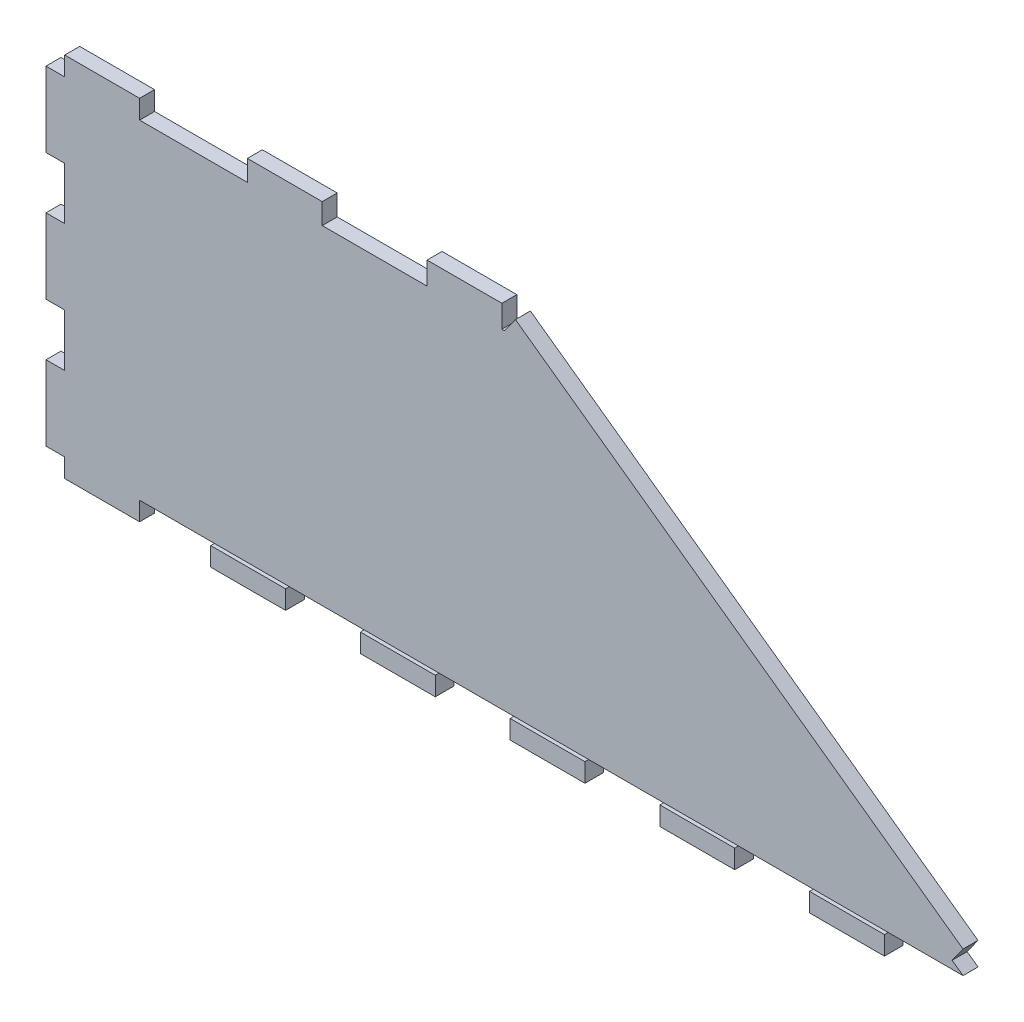
SolidWorks part; units mm, degrees
ref_plane "Front Plane" through (0, 0, 0) normal (0, 0, 1) x (1, 0, 0)
ref_plane "Top Plane" through (0, 0, 0) normal (0, 1, 0) x (1, 0, 0)
ref_plane "Right Plane" through (0, 0, 0) normal (1, 0, 0) x (0, 0, -1)
sketch "Sketch1" plane through (-5.3296, -16.203, 0) normal (0, 0, 1) x (1, 0, 0)
  line L0 (-139.4125, -47.2066) -> (-139.4125, -165.2411) construction
  line L1 (-294.9875, -47.2066) -> (-294.9875, -39.3326) construction
  line L2 (-294.9875, -47.2066) -> (-294.9875, -165.2411)
  line L3 (-294.9875, -165.2411) -> (16.1625, -165.2411) construction
  line L4 (16.1625, -158.8911) -> (16.1625, -165.2411)
  line L5 (-105.6158, -63.6519) -> (-109.3189, -68.8103) construction
  line L6 (-294.9875, -158.8911) -> (16.1625, -158.8911)
  line L7 (16.1625, -158.8911) -> (-139.4125, -47.2066)
  line L8 (-139.4125, -47.2066) -> (-294.9875, -47.2066)
  line L9 (16.1625, -158.8911) -> (16.1625, -151.0743) construction
  line L10 (-135.7094, -42.0482) -> (16.1625, -151.0743)
  line L11 (-139.4125, -47.2066) -> (-139.4125, -39.2968)
  line L12 (-139.4125, -39.2968) -> (-288.6375, -40.7811) construction
  line L13 (-288.6375, -165.2411) -> (-288.6375, -40.7811)
  line L14 (-139.4125, -47.2066) -> (-135.7094, -42.0482)
  line L15 (-139.4125, -39.2968) -> (-135.7094, -42.0482) construction
  line L16 (16.1625, -151.0743) -> (12.4593, -156.2327)
  line L17 (-135.7094, -42.0482) -> (-139.4125, -39.2968)
  line L18 (16.1625, -151.0743) -> (16.1625, -165.2411)
  line L19 (12.4593, -156.2327) -> (12.4593, -158.8911)
  line L21 (-288.6375, -165.2411) -> (-263.2375, -165.2411)
  line L22 (-288.6375, -165.2411) -> (-288.6375, -158.8911)
  line L23 (-288.6375, -158.8911) -> (-263.2375, -158.8911)
  line L24 (-263.2375, -165.2411) -> (-263.2375, -158.8911)
  line L25 (-237.8375, -158.8911) -> (-212.4375, -158.8911)
  line L26 (-237.8375, -158.8911) -> (-237.8375, -165.2411)
  line L27 (-237.8375, -165.2411) -> (-212.4375, -165.2411)
  line L28 (-212.4375, -158.8911) -> (-212.4375, -165.2411)
  line L29 (-187.0375, -158.8911) -> (-161.6375, -158.8911)
  line L30 (-187.0375, -158.8911) -> (-187.0375, -165.2411)
  line L31 (-187.0375, -165.2411) -> (-161.6375, -165.2411)
  line L32 (-161.6375, -158.8911) -> (-161.6375, -165.2411)
  line L33 (-136.2375, -158.8911) -> (-110.8375, -158.8911)
  line L34 (-136.2375, -158.8911) -> (-136.2375, -165.2411)
  line L35 (-136.2375, -165.2411) -> (-110.8375, -165.2411)
  line L36 (-110.8375, -158.8911) -> (-110.8375, -165.2411)
  line L37 (-85.4375, -158.8911) -> (-60.0375, -158.8911)
  line L38 (-85.4375, -158.8911) -> (-85.4375, -165.2411)
  line L39 (-85.4375, -165.2411) -> (-60.0375, -165.2411)
  line L40 (-60.0375, -158.8911) -> (-60.0375, -165.2411)
  line L41 (-34.6375, -158.8911) -> (-9.2375, -158.8911)
  line L42 (-34.6375, -158.8911) -> (-34.6375, -165.2411)
  line L43 (-34.6375, -165.2411) -> (-9.2375, -165.2411)
  line L44 (-9.2375, -158.8911) -> (-9.2375, -165.2411)
  line L45 (-294.9875, -47.2066) -> (-288.6375, -47.2066)
  line L46 (-294.9875, -47.2066) -> (-294.9875, -72.6066)
  line L47 (-294.9875, -72.6066) -> (-288.6375, -72.6066)
  line L48 (-288.6375, -47.2066) -> (-288.6375, -72.6066)
  line L49 (-294.9875, -158.8911) -> (-288.6375, -158.8911)
  line L50 (-294.9875, -158.8911) -> (-294.9875, -133.4911)
  line L51 (-294.9875, -133.4911) -> (-288.6375, -133.4911)
  line L52 (-288.6375, -158.8911) -> (-288.6375, -133.4911)
  line L53 (-294.9875, -115.7111) -> (-288.6375, -115.7111)
  line L54 (-294.9875, -115.7111) -> (-294.9875, -90.3111)
  line L55 (-294.9875, -90.3111) -> (-288.6375, -90.3111)
  line L56 (-288.6375, -115.7111) -> (-288.6375, -90.3111)
  line L57 (-288.6375, -40.7811) -> (-263.2375, -40.7811)
  line L58 (-288.6375, -40.7811) -> (-288.6375, -47.2066)
  line L59 (-288.6375, -47.2066) -> (-263.2375, -47.2066)
  line L60 (-263.2375, -40.7811) -> (-263.2375, -47.2066)
  line L61 (-226.6615, -40.1646) -> (-201.2615, -40.1646)
  line L62 (-226.6615, -40.1646) -> (-226.6615, -47.2066)
  line L63 (-226.6615, -47.2066) -> (-201.2615, -47.2066)
  line L64 (-201.2615, -40.1646) -> (-201.2615, -47.2066)
  line L65 (-165.7015, -39.5583) -> (-140.3015, -39.5583)
  line L66 (-165.7015, -39.5583) -> (-165.7015, -47.2066)
  line L67 (-165.7015, -47.2066) -> (-140.3015, -47.2066)
  line L68 (-140.3015, -39.5583) -> (-140.3015, -47.2066)
  point P32 (-161.6375, -162.0661)
  point P50 (-291.8125, -90.3111)
  point P61 (-226.6615, -43.6856)
  dimension "D1" = 6.35
  dimension "D2" = 311.15
  dimension "D3" = 6.35
  dimension "D4" = 7.874
  dimension "D5" = 6.35
  dimension "D6" = 124.46
  dimension "D7" = 25.4
  dimension "D8" = 25.4
  dimension "D9" = 25.4
  dimension "D10" = 25.4
  dimension "D11" = 25.4
  dimension "D12" = 25.4
  dimension "D13" = 25.4
  dimension "D14" = 25.4
  dimension "D15" = 25.4
  dimension "D16" = 25.4
  dimension "D17" = 25.4
  dimension "D18" = 25.4
  dimension "D19" = 25.4
  dimension "D20" = 25.4
  dimension "D21" = 17.78
  dimension "D22" = 25.4
  dimension "D23" = 25.4
  dimension "D24" = 25.4
  dimension "D25" = 36.576
  dimension "D26" = 35.56
extrude "Boss-Extrude1" add sketch "Sketch1" along normal blind 5.08 contours L16 L10 L14 L7 | L19 L7 L8 L13 L6 | L7 L19 L6 | L13 L3 L4 L6 | L13 L8 L11 L12 | L55 L2 L53 L13 | L2 L47 L13 L8 | L51 L2 L6 L13 | L64 L61 L62 L8 | L68 L65 L66 L8 region at (-297.1421, -76.1096, 0) region at (-281.2671, -60.1969, 0) region at (-176.0542, -125.6207, 0) region at (-297.1421, -119.2141, 0) region at (-219.2911, -59.8887, 0) region at (-297.1421, -162.3941, 0) region at (-158.3311, -59.5855, 0) region at (-281.2671, -178.2691, 0) region at (-66.9546, -115.3435, 0) region at (8.3641, -174.208, 0)
extrude "Boss-Extrude2" add sketch "Sketch1<4>" along normal blind 6.35 contours L28 L6 L26 L27 | L32 L6 L30 L31 | L36 L6 L34 L35 region at (-230.4671, -178.2691, 0) region at (-179.6671, -178.2691, 0) region at (-128.8671, -178.2691, 0)
sketch "Sketch1<4>" plane through (-5.3296, -16.203, 0) normal (0, 0, 1) x (1, 0, 0) same geometry as "Sketch1"
extrude "Boss-Extrude3" add sketch "Sketch1<5>" along normal blind 6.35 contours L40 L6 L38 L39 | L44 L6 L42 L43 region at (-27.2671, -178.2691, 0) region at (-78.0671, -178.2691, 0)
sketch "Sketch1<5>" plane through (-5.3296, -16.203, 0) normal (0, 0, 1) x (1, 0, 0) same geometry as "Sketch1"
